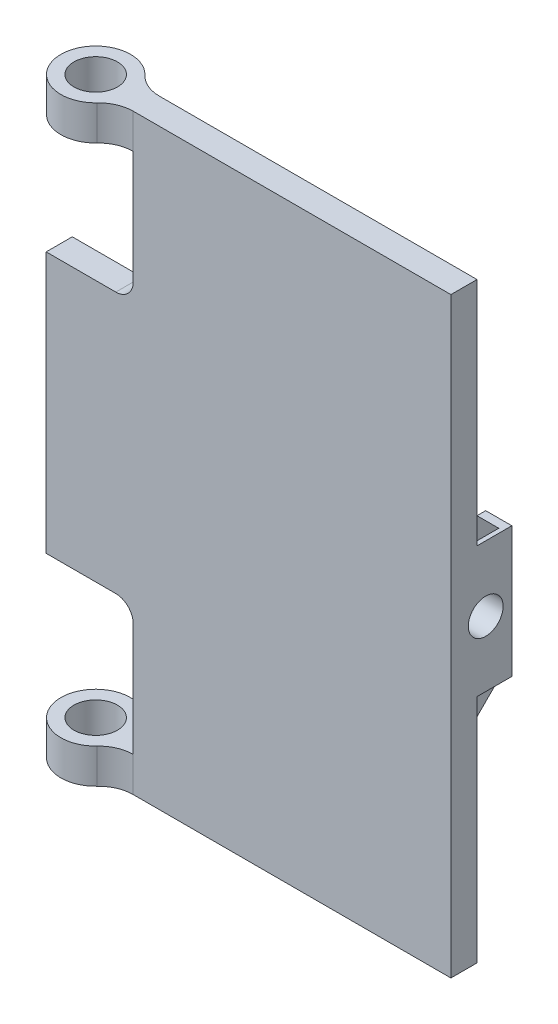
SolidWorks part; units mm, degrees
ref_plane "前视基准面" through (0, 0, 0) normal (0, 0, 1) x (1, 0, 0)
ref_plane "上视基准面" through (0, 0, 0) normal (0, 1, 0) x (1, 0, 0)
ref_plane "右视基准面" through (0, 0, 0) normal (1, 0, 0) x (0, 0, -1)
sketch "草图1" plane through (0, 0, 0) normal (0, 0, 1) x (1, 0, 0)
  line L1 (-18.25, 34) -> (18.25, 34)
  line L2 (-18.25, 34) -> (-18.25, -34)
  line L3 (-18.25, -34) -> (18.25, -34)
  line L4 (18.25, 34) -> (18.25, -34)
  line L5 (0, -34) -> (0, 34) construction
  line L6 (-18.25, 0) -> (18.25, 0) construction
  point P0 (0, 0)
  dimension "D1" = 68
  dimension "D2" = 36.5
extrude "凸台-拉伸1" add sketch "草图1" along normal blind 3
sketch "草图2" plane through (0, -34, 0) normal (0, -1, 0) x (1, 0, 0)
  line L0 (-18.25, 3) -> (-18.25, 0) construction
  line L1 (-18.25, 1.5) -> (-16.0565, 1.5) construction
  line L2 (-18.25, 3) -> (18.25, 3) construction
  line L4 (-18.25, 3) -> (-18.25, 0)
  arc A0 (-21.1547, 4.25) -> (-21.1547, -1.25) centre (-24.0595, 1.5) ccw
  arc A1 (-21.1547, 4.25) -> (-18.25, 3) centre (-18.25, 7) ccw
  arc A2 (-21.1547, -1.25) -> (-18.25, 0) centre (-18.25, -4) cw
  circle A3 centre (-24.0595, 1.5) radius 2.5
  point P1 (-28.0595, 1.5)
  point P5 (-18.25, 1.5)
  point P18 (-28.0595, 1.5)
  dimension "D1" = 4
  dimension "D2" = 8
  dimension "D3" = 5
extrude "凸台-拉伸2" add sketch "草图2" against normal blind 4
sketch "草图3" plane through (0, 34, 0) normal (0, 1, 0) x (1, 0, 0)
  line L1 (-18.25, -3) -> (-18.25, 0)
  line L2 (-18.25, -3) -> (-18.25, 0)
  arc A3 (-18.25, -3) -> (-21.1547, -4.25) centre (-18.25, -7) ccw
  arc A4 (-21.1547, 1.25) -> (-18.25, 0) centre (-18.25, 4) ccw
  arc A5 (-21.1547, 1.25) -> (-21.1547, -4.25) centre (-24.0595, -1.5) ccw
  arc A6 (-18.25, -3) -> (-21.1547, -4.25) centre (-18.25, -7) ccw
  arc A7 (-21.1547, 1.25) -> (-18.25, 0) centre (-18.25, 4) ccw
  arc A8 (-21.1547, 1.25) -> (-21.1547, -4.25) centre (-24.0595, -1.5) ccw
  dimension "D1" = 0
extrude "凸台-拉伸3" add sketch "草图3" against normal blind 4
sketch "草图4" plane through (0, 34, 0) normal (0, 1, 0) x (1, 0, 0)
  circle A0 centre (-24.0595, -1.5) radius 2.5
  dimension "D1" = 5
extrude "切除-拉伸1" cut sketch "草图4" against normal blind 4
sketch "草图5" plane through (0, 0, 0) normal (0, 0, -1) x (-1, 0, 0)
  line L0 (-18.25, -34) -> (-18.25, 34) construction
  line L1 (-18.25, 7.5) -> (-15.25, 7.5)
  line L2 (-18.25, 7.5) -> (-18.25, -7.5)
  line L3 (-18.25, -7.5) -> (-15.25, -7.5)
  line L4 (-15.25, 7.5) -> (-15.25, -7.5)
  point P6 (-18.25, 0)
  dimension "D1" = 3
  dimension "D2" = 15
extrude "凸台-拉伸4" add sketch "草图5" along normal blind 4
sketch "草图6" plane through (0, 0, 0) normal (0, 0, -1) x (-1, 0, 0)
  line L0 (-15.25, 7.5) -> (-15.25, 15)
  line L1 (-15.25, 15) -> (-3.25, 15)
  line L2 (-3.25, 15) -> (-3.25, -15)
  line L3 (0, 0) -> (8.8338, 0) construction
  line L4 (-15.25, -15) -> (-3.25, -15)
  line L5 (-15.25, -7.5) -> (-15.25, -15)
  line L6 (-15.25, 7.5) -> (-15.25, -7.5)
  point P9 (-3.25, 0)
  dimension "D1" = 30
  dimension "D2" = 12
extrude "切除-拉伸2" cut sketch "草图6" against normal blind 2
sketch "草图7" plane through (18.25, 0, 0) normal (1, 0, 0) x (0, 0, -1)
  line L0 (4, 7.5) -> (4, -7.5) construction
  circle A0 centre (1, 0) radius 2
  dimension "D1" = 4
  dimension "D2" = 3
extrude "切除-拉伸3" cut sketch "草图7" against normal blind 5
ref_plane "基准面1" through (16.75, 0, 0) normal (-1, 0, 0) x (0, 0, 1)
sketch "草图8" plane through (16.75, 0, 0) normal (-1, 0, 0) x (0, 0, 1)
  line L0 (-3, 7.5) -> (0, 10.5)
  line L1 (-4, 7.5) -> (0, 7.5) construction
  line L2 (0, 30) -> (0, -30) construction
  line L3 (0, 10.5) -> (0, 7.5)
  line L4 (0, 7.5) -> (-3, 7.5)
  dimension "D1" = 3
extrude "凸台-拉伸5" add sketch "草图8" along normal mid plane 2
mirror "镜向1" about plane through (0, 0, 0) normal (0, 1, 0) of "凸台-拉伸5"
sketch "草图9" plane through (0, 0, 3) normal (0, 0, 1) x (1, 0, 0)
  line L0 (-18.25, 15) -> (-28.25, 15)
  line L1 (-18.25, 30) -> (-18.25, -30) construction
  line L2 (-28.25, 15) -> (-28.25, -15)
  line L3 (-28.25, -15) -> (-18.25, -15)
  line L4 (-18.25, 15) -> (-18.25, -15)
  point P5 (-28.25, 0)
  dimension "D1" = 30
  dimension "D2" = 10
extrude "凸台-拉伸6" add sketch "草图9" against normal blind 3
fillet "圆角1" radius 2 2 edges at (-18.25, 15, 1.5) (-18.25, -15, 1.5)
fillet "圆角2" radius 1 1 edges at (15.25, 0, 2)
